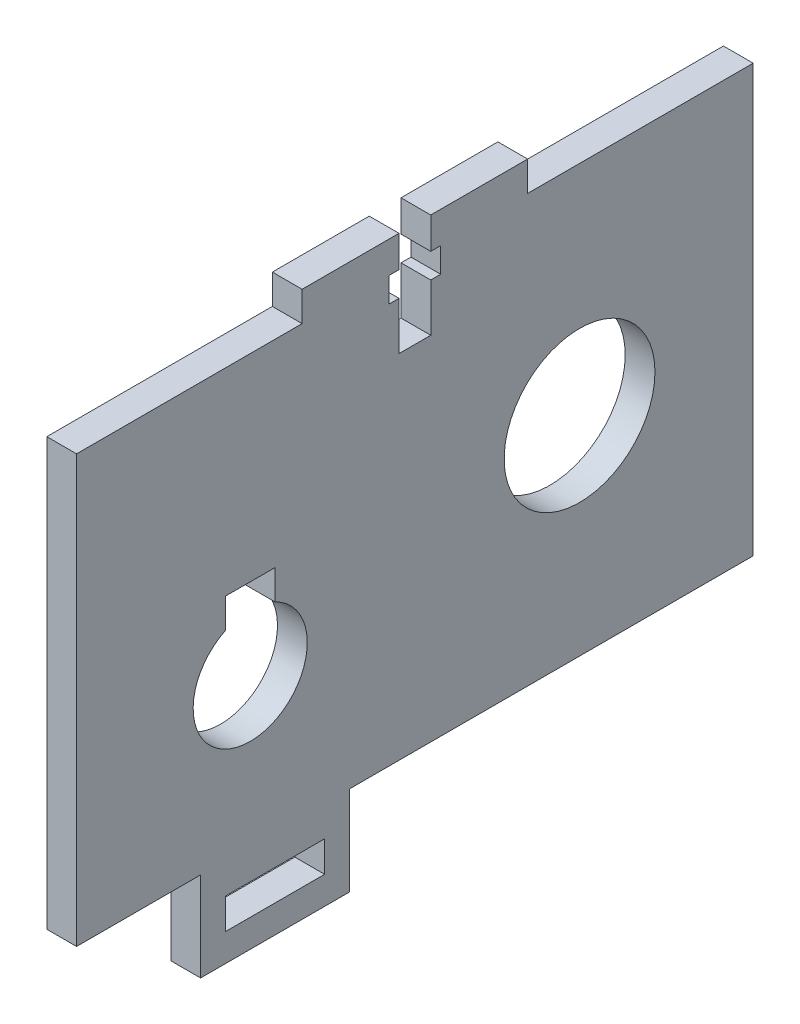
SolidWorks part; units mm, degrees
note: '?' marks a value the reader was unsure of.
ref_plane "Front Plane" through (0, 0, 0) normal (0, 0, 1) x (1, 0, 0)
ref_plane "Top Plane" through (0, 0, 0) normal (0, 1, 0) x (1, 0, 0)
ref_plane "Right Plane" through (0, 0, 0) normal (1, 0, 0) x (0, 0, -1)
sketch "Sketch1" plane through (0, 0, 0) normal (1, 0, 0) x (0, 0, -1)
  line L0 (0, 0) -> (0, 46)
  line L12 (0, 0) -> (12.5, 0)
  line L17 (12.5, 0) -> (12.5, -9)
  line L18 (12.5, -9) -> (27.5, -9)
  line L19 (27.5, -9) -> (27.5, 0)
  line L20 (0, 46) -> (22.7313, 46)
  line L21 (22.7313, 46) -> (22.7313, 43)
  line L22 (22.7313, 43) -> (45.4625, 43)
  line L23 (45.4625, 43) -> (45.4625, 46)
  line L24 (45.4625, 46) -> (68.1938, 46)
  line L25 (68.1938, 46) -> (68.1938, 0)
  line L41 (15, -6.2) -> (25, -6.2)
  line L42 (15, -6.2) -> (15, -3.1)
  line L43 (15, -3.1) -> (25, -3.1)
  line L44 (25, -6.2) -> (25, -3.1)
  line L45 (15, -6.2) -> (25, -3.1) construction
  line L46 (15, -3.1) -> (25, -6.2) construction
  line L49 (27.5, 0) -> (68.1938, 0)
  line L50 (0, 43) -> (22.7313, 43)
  line L51 (22.7313, 46) -> (45.4625, 46)
  line L53 (45.4625, 43) -> (68.1938, 43)
  circle A1 centre (50.6938, 21) radius 7.6
  circle A2 centre (17.5, 14.8978) radius 5.75
  point P14 (20, -4.65)
  point P20 (20, -9)
  point P41 (17.5, 14.8978)
  point P42 (50.6938, 21)
  dimension "D10" = 20
  dimension "D11" = 15.2
  dimension "D2" = 14.8978
  dimension "D13" = 11.5
  dimension "D3" = 9
  dimension "D4" = 21
  dimension "D5" = 33.75
  dimension "D6" = 17.5
  dimension "D7" = 46
  dimension "D8" = 17.5
  dimension "D9" = 3
  dimension "D12" = 3.1
  dimension "D15" = 15
  dimension "D17" = 10
  dimension "D18" = 3.1
extrude "Boss-Extrude1" add sketch "Sketch1" along normal blind 3
sketch "Sketch2" plane through (3, 0, 0) normal (1, 0, 0) x (0, 0, -1)
  line L0 (15, 20.0759) -> (15, 23.0759)
  line L1 (31.4969, 40.325) -> (36.6969, 40.325)
  line L2 (31.4969, 40.325) -> (31.4969, 42.825)
  line L3 (31.4969, 42.825) -> (36.6969, 42.825)
  line L4 (36.6969, 40.325) -> (36.6969, 42.825)
  line L5 (31.4969, 40.325) -> (36.6969, 42.825) construction
  line L6 (31.4969, 42.825) -> (36.6969, 40.325) construction
  line L7 (32.4969, 46) -> (35.6969, 46)
  line L8 (32.4969, 46) -> (32.4969, 35.5)
  line L9 (32.4969, 35.5) -> (35.6969, 35.5)
  line L10 (35.6969, 46) -> (35.6969, 35.5)
  line L11 (32.4969, 46) -> (35.6969, 35.5) construction
  line L12 (32.4969, 35.5) -> (35.6969, 46) construction
  line L23 (15, 23.0759) -> (20, 23.0759)
  line L24 (20, 23.0759) -> (20, 20.0759)
  line L27 (22.7313, 46) -> (45.4625, 46) construction
  arc A0 (15, 20.0759) -> (20, 20.0759) centre (17.5, 14.8978) cw
  circle A1 centre (17.5, 14.8978) radius 5.75 construction
  point P0 (34.0969, 41.575)
  point P5 (34.0969, 40.75)
  point P20 (34.0969, 46)
  dimension "D1" = 10.5
  dimension "D2" = 3.2
  dimension "D3" = 5.2
  dimension "D4" = 3.175
  dimension "D5" = 2.5
  dimension "D7" = 3
  dimension "D8" = 5
extrude "Cut-Extrude1" cut sketch "Sketch2" against normal through all both and the other way through all
ref_axis "Axis1" through (-14.2531, 14.8978, -17.5) along (1, 0, 0)?
ref_axis "Axis2" through (-11.3678, 21, -50.6938) along (1, 0, 0)?
